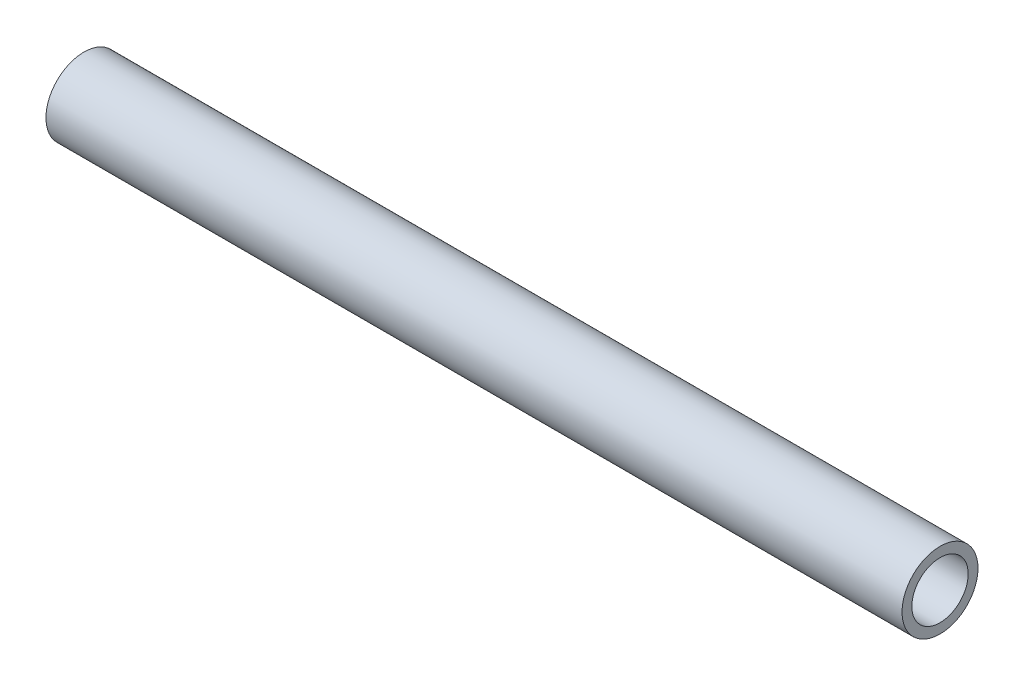
SolidWorks part; units mm, degrees
material "PVC Rígido"
ref_plane "Alzado" through (0, 0, 0) normal (0, 0, 1) x (1, 0, 0)
ref_plane "Planta" through (0, 0, 0) normal (0, 1, 0) x (1, 0, 0)
ref_plane "Vista lateral" through (0, 0, 0) normal (1, 0, 0) x (0, 0, -1)
sketch "Croquis1" plane through (0, 0, 0) normal (1, 0, 0) x (0, 0, -1)
  circle A0 centre (0, 0) radius 10.65
  circle A1 centre (0, 0) radius 7.9
  dimension "D1" = 21.3
  dimension "D2" = 15.8
extrude "Saliente-Extruir1" add sketch "Croquis1" along normal blind 240
